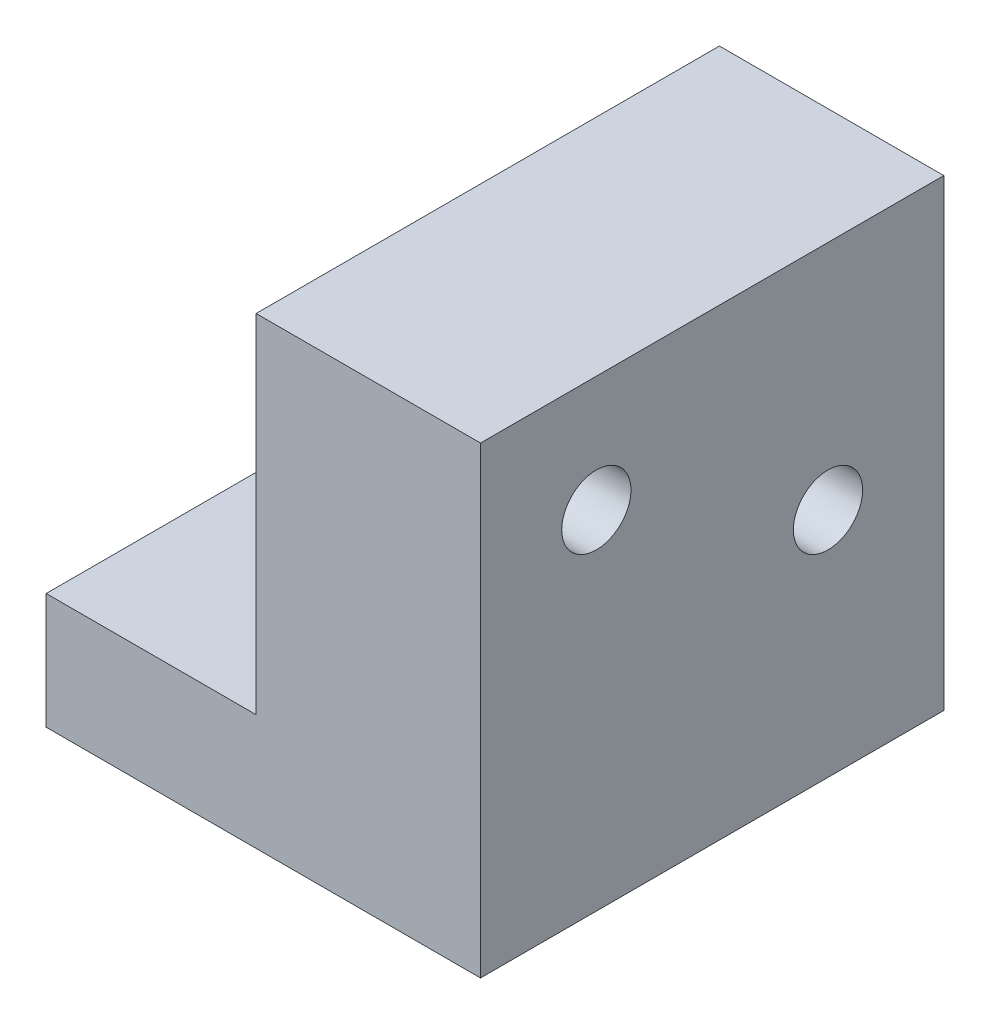
SolidWorks part; units mm, degrees
material "DELRIN (WHITE)"
ref_plane "Front" through (0, 0, 0) normal (0, 0, 1) x (1, 0, 0)
ref_plane "Top" through (0, 0, 0) normal (0, 1, 0) x (1, 0, 0)
ref_plane "Right" through (0, 0, 0) normal (1, 0, 0) x (0, 0, -1)
ref_axis "Axis1" through (0, 50, 0) along (0, -1, 0)
sketch "Sketch1" plane through (0, 0, 0) normal (1, 0, 0) x (0, 0, -1)
  line L1 (-12.7, 12.7) -> (12.7, 12.7)
  line L2 (-12.7, 12.7) -> (-12.7, -12.7)
  line L3 (-12.7, -12.7) -> (12.7, -12.7)
  line L4 (12.7, 12.7) -> (12.7, -12.7)
  line L5 (-12.7, 12.7) -> (12.7, -12.7) construction
  line L6 (-12.7, -12.7) -> (12.7, 12.7) construction
  point P0 (0, 0)
  dimension "D1" = 25.4
  dimension "D2" = 25.4
extrude "Extrude1" add sketch "Sketch1" against normal blind 23.8125
sketch "Sketch2" plane through (0, 0, 12.7) normal (0, 0, 1) x (1, 0, 0)
  line L1 (-23.8125, 12.7) -> (-12.3031, 12.7)
  line L2 (-23.8125, 12.7) -> (-23.8125, -6.35)
  line L3 (-23.8125, -6.35) -> (-12.3031, -6.35)
  line L4 (-12.3031, 12.7) -> (-12.3031, -6.35)
  line L5 (-23.8125, -12.7) -> (0, -12.7) construction
  line L7 (-23.8125, 12.7) -> (-23.8125, -12.7) construction
  line L8 (0, 12.7) -> (0, -12.7) construction
  line L9 (-23.8125, 12.7) -> (0, 12.7) construction
  dimension "D1" = 12.3031
  dimension "D2" = 6.35
extrude "Extrude2" cut sketch "Sketch2" against normal through all
hole_wizard "#10-24 Tapped Hole1" positions "Sketch4" profile "Sketch3" tap size "#10-24" standard "Ansi Inch" end condition through all
sketch "Sketch4" plane through (-23.8125, 0.158, -0.5769) normal (1, 0, 0) x (0, 0, -1)
  line L0 (-13.2769, -12.858) -> (12.1231, -12.858) construction
  line L1 (-13.2769, 12.542) -> (-13.2769, -12.858) construction
  point P0 (5.7731, -0.158)
  point P1 (-6.9269, 6.192)
  dimension "D1" = 12.7
  dimension "D2" = 12.7
  dimension "D3" = 6.35
  dimension "D4" = 6.35
sketch "Sketch3" plane through (-23.8125, 0, -6.35) normal (0, 1, 0) x (0, 0, 1)
  line L0 (0, 0) -> (0, 23.8125)
  line L1 (0, 23.8125) -> (1.8986, 23.8125)
  line L2 (1.8986, 23.8125) -> (1.8986, 0)
  line L5 (1.8986, 0) -> (0, 0)
  line L11 (0, -6.35) -> (0, 107.95) construction
  dimension "Thru Tap Drill Dia." = 3.7973
  dimension "Thru Tap Drill Depth" = 23.8125
cosmetic thread "Hole Thread1" parameters "D2"=4.826
cosmetic thread "Hole Thread2" parameters "D2"=4.826
